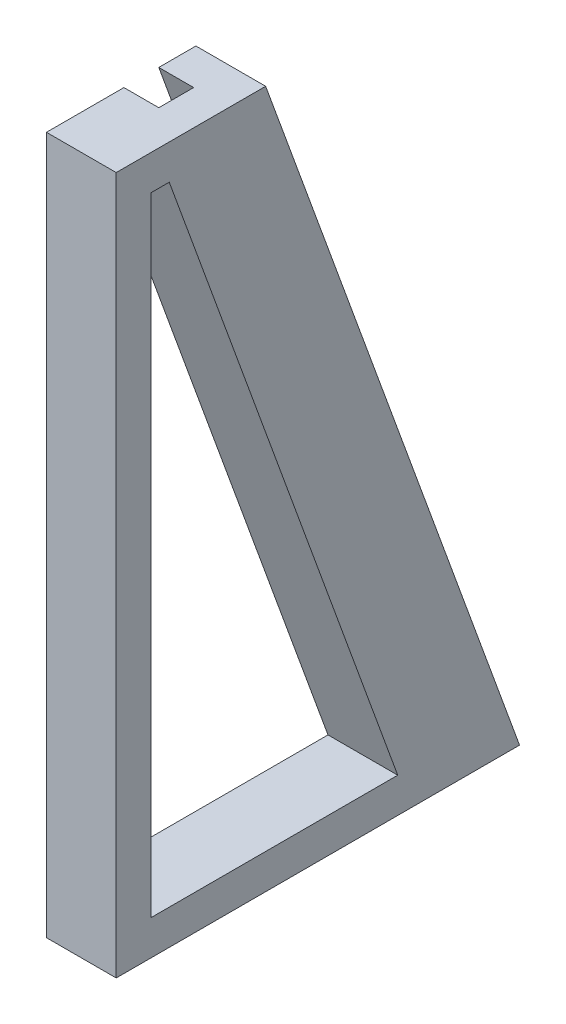
SolidWorks part; units mm, degrees
note: The reader was unsure of these and kept them because the rebuilt part matched: shared geometry of "Sketch2<3>".
ref_plane "Front Plane" through (0, 0, 0) normal (0, 0, 1) x (1, 0, 0)
ref_plane "Top Plane" through (0, 0, 0) normal (0, 1, 0) x (1, 0, 0)
ref_plane "Right Plane" through (0, 0, 0) normal (1, 0, 0) x (0, 0, -1)
sketch "Sketch1" plane through (0, 0, 0) normal (1, 0, 0) x (0, 0, -1)
  line L1 (-50, 50) -> (50, 50)
  line L2 (-50, 50) -> (-50, -50)
  line L3 (-50, -50) -> (50, -50)
  line L4 (50, 50) -> (50, -50)
  line L5 (-50, 50) -> (50, -50) construction
  line L6 (-50, -50) -> (50, 50) construction
  point P0 (0, 0)
  dimension "D1" = 100
  dimension "D2" = 100
extrude "Boss-Extrude1" add sketch "Sketch1" along normal blind 10
sketch "Sketch2" plane through (0, 0, 0) normal (-1, 0, 0) x (0, 0, 1)
  line L0 (-50, -50) -> (-50, 50)
  line L1 (-50, 50) -> (50, 50)
  line L2 (50, 50) -> (50, -50)
  line L3 (50, -50) -> (-50, -50)
  line L4 (38.897, 50) -> (50, 50)
  line L5 (0, -50) -> (2.5, -50)
  line L6 (0, -50) -> (-2.5, -50)
  line L7 (36.397, 50) -> (38.897, 50)
  line L8 (36.397, 50) -> (33.897, 50)
  line L9 (33.897, 50) -> (-2.5, -50)
  line L10 (38.897, 50) -> (2.5, -50)
  line L11 (50, -50) -> (50, 50)
  line L12 (50, -50) -> (2.5, -50)
  line L13 (2.5, -50) -> (38.897, 50)
  line L14 (7.1985, -51.7101) -> (7.8209, -50)
  line L15 (45, 45) -> (45, -45)
  line L16 (45, -45) -> (9.6407, -45)
  line L17 (9.6407, -45) -> (42.3981, 45)
  line L18 (50, -45) -> (-45, -45) construction
  line L19 (7.1985, -51.7101) -> (43.5955, 48.2899) construction
  line L20 (45, 50) -> (45, -50) construction
  line L21 (42.3981, 45) -> (45, 45)
  line L22 (-45, 45) -> (50, 45) construction
  line L23 (-0.6801, -45) -> (4.3199, -45)
  line L24 (-45, -45) -> (-45, 45) construction
  line M19 (50, 50) -> (-50, 50)
  dimension "D1" = 5
  dimension "D2" = 2.5
  dimension "D3" = 2.5
  dimension "D4" = 70
extrude "Cut-Extrude1" cut sketch "Sketch2" against normal blind 10 contours L21 L17 L16 L15
extrude "Cut-Extrude2" cut sketch "Sketch2<3>" against normal blind 5 contours L10 L1 L9 L3 M19
sketch "Sketch2<3>" plane through (0, 0, 0) normal (-1, 0, 0) x (0, 0, 1) same geometry as "Sketch2"
sketch "Sketch3" plane through (0, -50, 0) normal (0, -1, 0) x (1, 0, 0)
  line L0 (10, 50) -> (10, -50)
sketch "Sketch4" plane through (0, -50, 0) normal (0, -1, 0) x (1, 0, 0)
  line L0 (10, 50) -> (10, -50)
  line L1 (10, -50) -> (0, -50)
  line L2 (0, -50) -> (0, 50)
  line L3 (0, 50) -> (10, 50)
  line L4 (0, 50) -> (0, 40)
  line L5 (0, 40) -> (10, 40)
  line L6 (10, 40) -> (10, 50)
  line L7 (10, -50) -> (10, -40)
  line L8 (10, -40) -> (0, -40)
  line L9 (0, -40) -> (0, -50)
  line L10 (10, 0) -> (0, 0)
  line L11 (10, 0) -> (10, 0.3209)
  line L12 (10, 0.3209) -> (0, 0.3209)
  line L13 (0, 0.3209) -> (0, 0)
  line L14 (0, 0.3209) -> (0, 10.3209)
  line L15 (0, 10.3209) -> (10, 10.3209)
  line L16 (10, 10.3209) -> (10, 0.3209)
  line L17 (10, 10.3209) -> (10, 5.3209)
  line L18 (10, 45) -> (5, 45)
  line L19 (5, 45) -> (5, 50)
  line L20 (8, 8.3209) -> (2, 8.3209)
  line L21 (8, 8.3209) -> (8, 2.3209)
  line L22 (8, 2.3209) -> (2, 2.3209)
  line L23 (2, 8.3209) -> (2, 2.3209)
  line L24 (8, 8.3209) -> (2, 2.3209) construction
  line L25 (8, 2.3209) -> (2, 8.3209) construction
  line L26 (8, -42) -> (2, -42)
  line L27 (8, 48) -> (2, 48)
  line L28 (8, 48) -> (8, 42)
  line L29 (8, 42) -> (2, 42)
  line L30 (2, 48) -> (2, 42)
  line L31 (8, 48) -> (2, 42) construction
  line L32 (8, 42) -> (2, 48) construction
  line L33 (2, -48) -> (2, -42)
  line L34 (8, -48) -> (2, -48)
  line L35 (8, -48) -> (8, -42)
  line L36 (5, 5.3209) -> (10, 5.3209)
  line L37 (5, 5.3209) -> (5, 0.3209)
  line L38 (5, -50) -> (5, -45)
  line L39 (5, -45) -> (10, -45)
  dimension "D1" = 6
  dimension "D2" = 6
  dimension "D3" = 6
  dimension "D4" = 6
extrude "Cut-Extrude3" cut sketch "Sketch4" against normal blind 4 contours L34 L35 L26 L33 | L20 L23 L22 L21 | L27 L30 L29 L28 L18 L19 | L28 L27 L19 L18 | L36 L37 L22 L21 | L39 L38 L34 L35
sketch "Sketch5" plane through (0, 0, 0) normal (-1, 0, 0) x (0, 0, 1)
  line L0 (-50, 50) -> (33.897, 50)
  line L2 (-2.5, -50) -> (-50, -50)
  line L3 (-50, -50) -> (-50, 50)
  line L4 (33.897, 50) -> (-2.5, -50)
  line L6 (26.7563, 45) -> (-6.001, -45)
  line L9 (26.7563, 45) -> (28.5761, 50)
  line L10 (-6.001, -45) -> (-7.8209, -50)
  line L12 (-6.001, -45) -> (-45, -45) construction
  line L13 (-45, -45) -> (-45, 45) construction
  line L14 (-45, 45) -> (26.7563, 45) construction
  line M18 (-50, 50) -> (-50, -50)
  line M19 (-50, -50) -> (50, -50)
  dimension "D1" = 5
  dimension "D2" = 180
  dimension "D3" = 180
extrude "Cut-Extrude4" cut sketch "Sketch5" against normal blind 10 contours L10 L6 L9 L0 M18 M19
